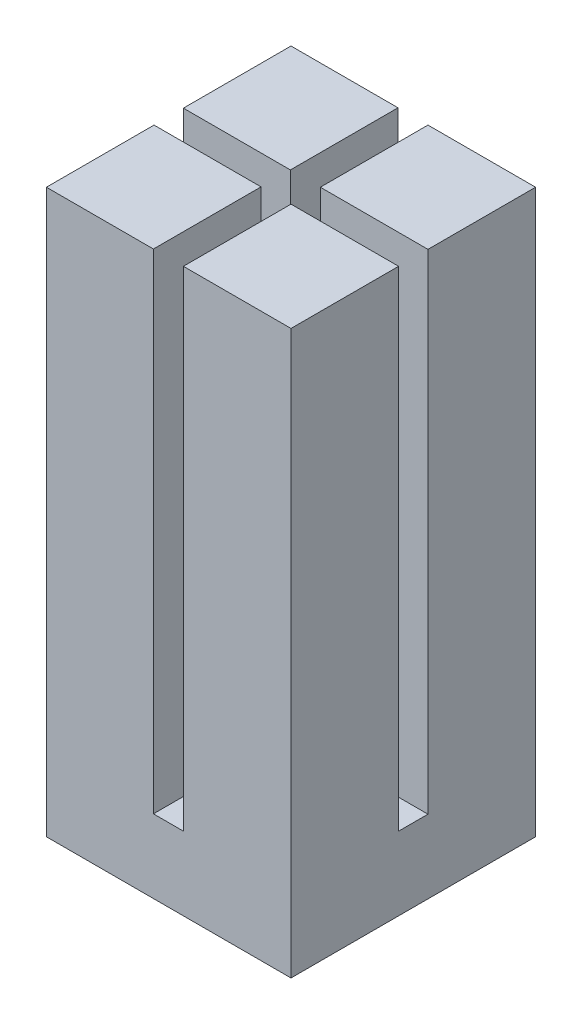
SolidWorks part; units mm, degrees
ref_plane "Front Plane" through (0, 0, 0) normal (0, 0, 1) x (1, 0, 0)
ref_plane "Top Plane" through (0, 0, 0) normal (0, 1, 0) x (1, 0, 0)
ref_plane "Right Plane" through (0, 0, 0) normal (1, 0, 0) x (0, 0, -1)
sketch "Sketch1" plane through (0, 0, 0) normal (0, 1, 0) x (1, 0, 0)
  line L0 (-12.7, 12.7) -> (-12.7, 1.524)
  line L1 (-12.7, 12.7) -> (12.7, 12.7)
  line L2 (-12.7, 12.7) -> (-12.7, -12.7)
  line L3 (-12.7, -12.7) -> (12.7, -12.7)
  line L4 (12.7, 12.7) -> (12.7, -12.7)
  line L5 (-12.7, 12.7) -> (12.7, -12.7) construction
  line L6 (-12.7, -12.7) -> (12.7, 12.7) construction
  line L7 (-1.5875, 12.7) -> (-1.5875, -12.7)
  line L8 (-1.5875, 12.7) -> (1.0048, 12.7)
  line L9 (-12.7, 12.5473) -> (-12.7, 1.3928)
  line L10 (-12.7, 1.524) -> (12.7, 1.524)
  line L11 (-12.7, -12.7) -> (-12.7, -1.524)
  line L12 (-12.7, -1.524) -> (12.7, -1.524)
  line L13 (12.7, -12.7) -> (1.524, -12.7)
  line L14 (1.524, -12.7) -> (1.524, 12.7)
  point P0 (0, 0)
  point P20 (0, 0)
  dimension "D1" = 25.4
  dimension "D2" = 25.4
  dimension "D3" = 11.1125
  dimension "D4" = 11.176
  dimension "D5" = 25.4
  dimension "D6" = 11.176
  dimension "D7" = 25.4
  dimension "D8" = 11.176
  dimension "D9" = 25.4
extrude "Boss-Extrude1" add sketch "Sketch1" along normal blind 50.8 contours L2 L10 L7 L1 L0 | L12 L2 L3 L7 | L14 L10 L4 L1 | L14 L3 L4 L12 region at (-7.1438, 0, -7.112) region at (7.112, 0, -7.112) region at (-7.1438, 0, 7.112) region at (7.112, 0, 7.112)
ref_plane "Plane1" through (1.524, 0, -1.524) normal (0, -1, 0) x (-1, 0, 0)
ref_plane "Plane2" through (-1.5875, 0, -1.524) normal (0, -1, 0) x (-1, 0, 0)
extrude "Boss-Extrude2" add sketch "Sketch1<4>" against normal blind 7.62 contours L4 L3 L2 L1
sketch "Sketch1<4>" plane through (0, 0, 0) normal (0, 1, 0) x (1, 0, 0) same geometry as "Sketch1"
